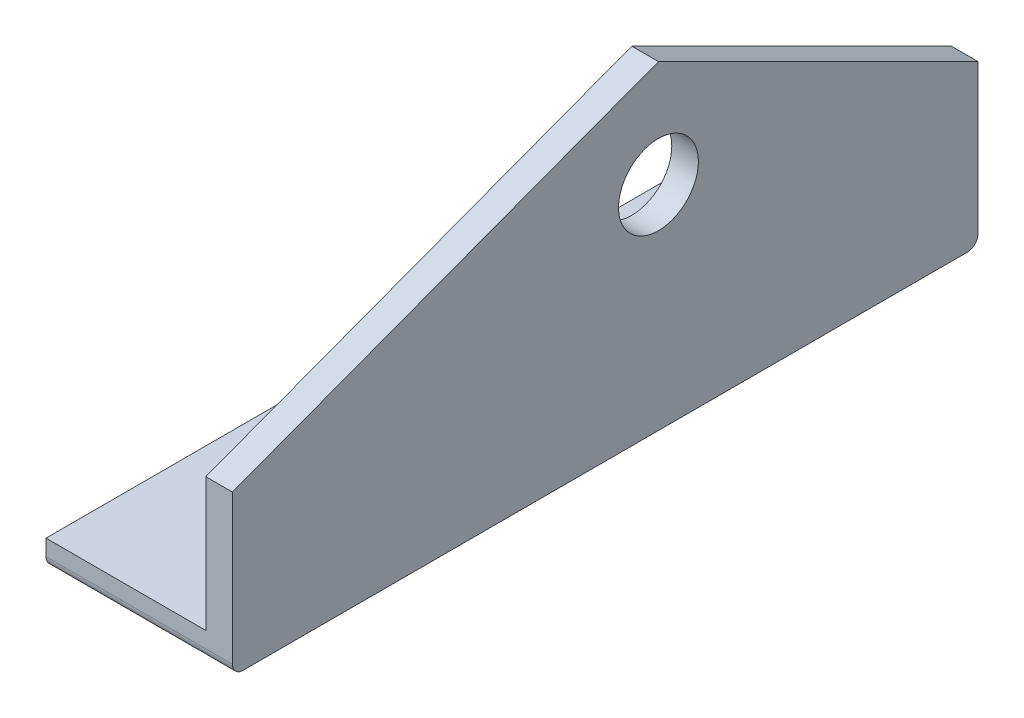
SolidWorks part; units mm, degrees
material "ABS"
ref_plane "Front Plane" through (0, 0, 0) normal (0, 0, 1) x (1, 0, 0)
ref_plane "Top Plane" through (0, 0, 0) normal (0, 1, 0) x (1, 0, 0)
ref_plane "Right Plane" through (0, 0, 0) normal (1, 0, 0) x (0, 0, -1)
sketch "Sketch1" plane through (0, 0, 0) normal (1, 0, 0) x (0, 0, -1)
  line L0 (0, 20) -> (-80, -10)
  line L1 (-80, -10) -> (-80, -40)
  line L2 (-80, -40) -> (60, -40)
  line L3 (60, -40) -> (60, -10)
  line L4 (60, -10) -> (0, 20)
  circle A0 centre (0, 0) radius 7.5
  dimension "D1" = 15
  dimension "D6" = 40
  dimension "D2" = 140
  dimension "D3" = 80
  dimension "D4" = 60
  dimension "D5" = 30
extrude "Boss-Extrude1" add sketch "Sketch1" along normal blind 5
sketch "Sketch3" plane through (5, 0, 0) normal (1, 0, 0) x (0, 0, -1)
  line L0 (60, -40) -> (60, -10) construction
  line L1 (-80, -40) -> (60, -40)
  line L2 (-80, -40) -> (-80, -35)
  line L3 (-80, -35) -> (60, -35)
  line L4 (60, -40) -> (60, -35)
  dimension "D1" = 5
extrude "Boss-Extrude2" [suppressed] add sketch "Sketch3" along normal blind 30
extrude "Boss-Extrude3" add sketch "Sketch3<2>" against normal blind 35 contours L3 L4 L1 L2
sketch "Sketch3<2>" plane through (5, 0, 0) normal (1, 0, 0) x (0, 0, -1) same geometry as "Sketch3"
fillet "Fillet1" radius 2 2 edges at (-12.5, -40, -60) (-12.5, -40, 80)
